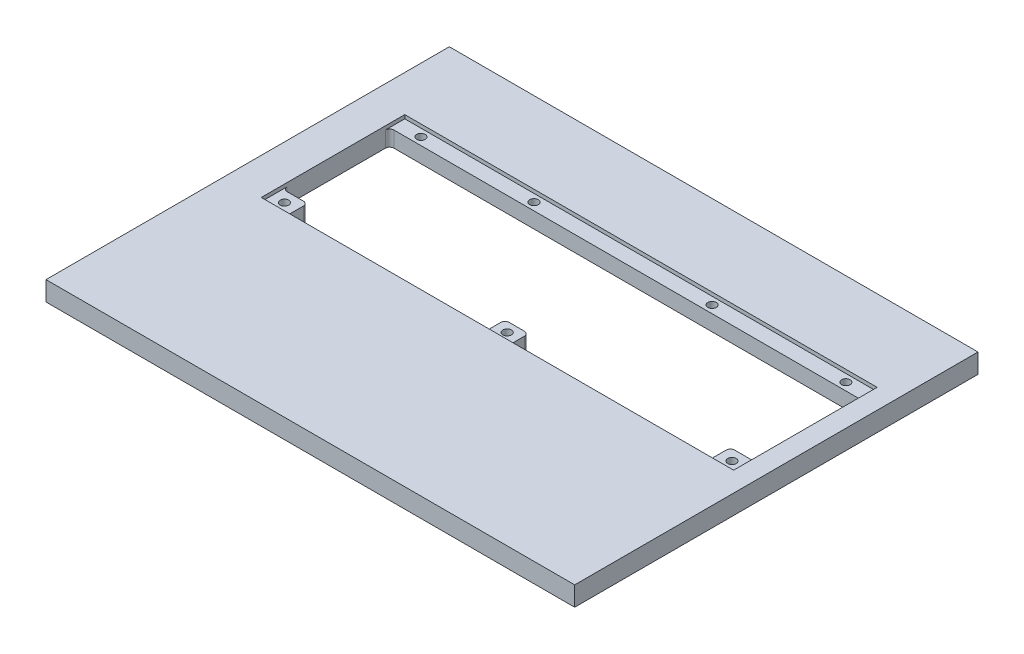
SolidWorks part; units mm, degrees
ref_plane "Front Plane" through (0, 0, 0) normal (0, 0, 1) x (1, 0, 0)
ref_plane "Top Plane" through (0, 0, 0) normal (0, 1, 0) x (1, 0, 0)
ref_plane "Right Plane" through (0, 0, 0) normal (1, 0, 0) x (0, 0, -1)
sketch "Sketch1" plane through (0, 0, 0) normal (0, 1, 0) x (1, 0, 0)
  line L1 (0, 0) -> (245, 0)
  line L2 (0, 0) -> (0, 186.9)
  line L3 (0, 186.9) -> (245, 186.9)
  line L4 (245, 0) -> (245, 186.9)
  dimension "D1" = 186.9
  dimension "D2" = 245
extrude "Boss-Extrude1" add sketch "Sketch1" along normal blind 9
sketch "Sketch2" plane through (0, 0, 0) normal (0, 1, 0) x (1, 0, 0)
  line L0 (245, 186.9) -> (0, 186.9) construction
  line L1 (16.91, 149.35) -> (235.81, 149.35)
  line L2 (16.91, 149.35) -> (16.91, 82.85)
  line L3 (16.91, 82.85) -> (235.81, 82.85)
  line L4 (235.81, 149.35) -> (235.81, 82.85)
  dimension "D1" = 37.55
  dimension "D3" = 66.5
  dimension "D4" = 218.9
extrude "Cut-Extrude1" cut sketch "Sketch2" along normal blind 9
sketch "Sketch3" plane through (0, 9, 0) normal (0, 1, 0) x (1, 0, 0)
  line L0 (235.81, 149.35) -> (16.91, 149.35) construction
  line L1 (16.91, 149.35) -> (16.91, 82.85) construction
  line L2 (16.91, 82.85) -> (235.81, 82.85) construction
  circle A0 centre (27.91, 145.85) radius 2
  circle A1 centre (80.31, 145.85) radius 2
  circle A2 centre (162.81, 145.85) radius 2
  circle A3 centre (224.81, 145.85) radius 2
  circle A4 centre (22.66, 87.85) radius 2
  circle A5 centre (126.36, 87.35) radius 2
  circle A6 centre (230.06, 87.85) radius 2
  dimension "D3" = 4
  dimension "D4" = 3.5
  dimension "D6" = 3.5
  dimension "D8" = 3.5
  dimension "D10" = 5
  dimension "D12" = 4.5
  dimension "D14" = 5
  dimension "D1" = 3.5
  dimension "D2" = 11
  dimension "D5" = 52.4
  dimension "D7" = 82.5
  dimension "D9" = 62
  dimension "D11" = 5.75
  dimension "D13" = 103.7
  dimension "D15" = 103.7
sketch "Sketch4" plane through (0, 0, 0) normal (0, 1, 0) x (1, 0, 0)
  line L0 (235.81, 82.85) -> (235.81, 149.35) construction
  line L1 (16.91, 149.35) -> (235.81, 149.35)
  line L2 (16.91, 149.35) -> (16.91, 142.35)
  line L3 (16.91, 142.35) -> (235.81, 142.35)
  line L4 (235.81, 149.35) -> (235.81, 142.35)
  line L5 (16.91, 82.85) -> (235.81, 82.85) construction
  line L6 (235.81, 82.85) -> (224.31, 82.85)
  line L7 (235.81, 82.85) -> (235.81, 92.85)
  line L8 (235.81, 92.85) -> (224.31, 92.85)
  line L9 (224.31, 82.85) -> (224.31, 92.85)
  line L10 (120.86, 82.85) -> (131.86, 82.85)
  line L11 (120.86, 82.85) -> (120.86, 91.85)
  line L12 (120.86, 91.85) -> (131.86, 91.85)
  line L13 (131.86, 82.85) -> (131.86, 91.85)
  line L15 (16.91, 82.85) -> (28.41, 82.85)
  line L16 (16.91, 82.85) -> (16.91, 92.85)
  line L17 (16.91, 92.85) -> (28.41, 92.85)
  line L18 (28.41, 82.85) -> (28.41, 92.85)
  dimension "D1" = 7
  dimension "D2" = 5
  dimension "D3" = 5.75
  dimension "D4" = 4.5
  dimension "D5" = 5.5
  dimension "D6" = 5.5
  dimension "D7" = 5.75
  dimension "D8" = 5
extrude "Boss-Extrude2" add sketch "Sketch4" along normal blind 7.3
extrude "Cut-Extrude2" cut sketch "Sketch3" against normal blind 6.6
fillet "Fillet1" radius 2 12 edges at (16.91, 3.65, -92.85) (28.41, 3.65, -82.85) (28.41, 3.65, -92.85) (16.91, 3.65, -142.35) (235.81, 3.65, -142.35) (235.81, 3.65, -92.85) (224.31, 3.65, -82.85) (224.31, 3.65, -92.85) (120.86, 3.65, -82.85) (131.86, 3.65, -82.85) (131.86, 3.65, -91.85) (120.86, 3.65, -91.85)
